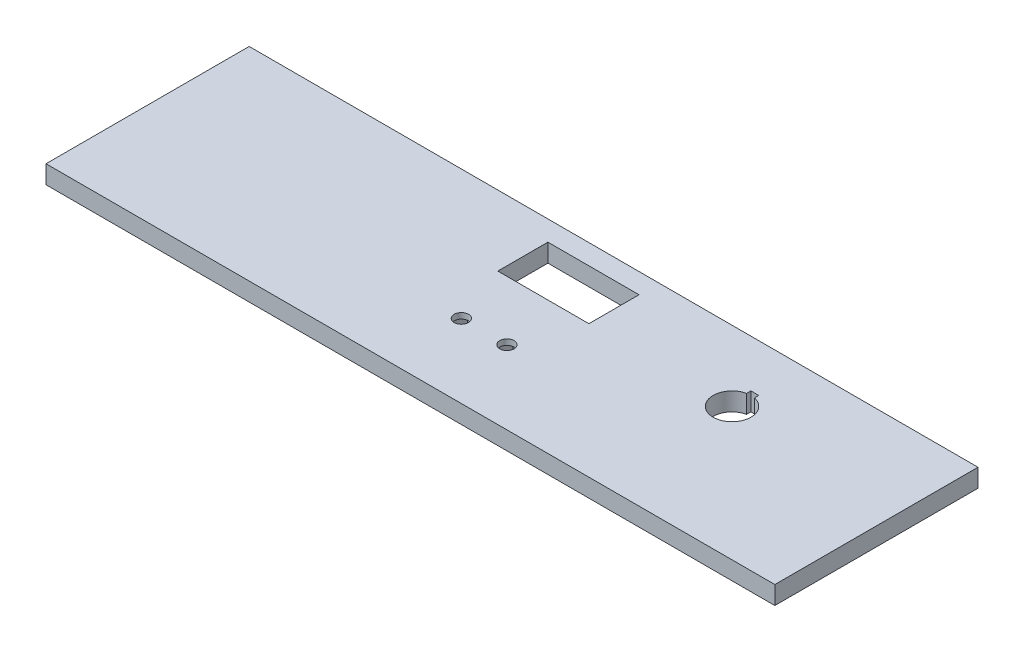
SolidWorks part; units mm, degrees
ref_plane "Front" through (0, 0, 0) normal (0, 0, 1) x (1, 0, 0)
ref_plane "Top" through (0, 0, 0) normal (0, 1, 0) x (1, 0, 0)
ref_plane "Right" through (0, 0, 0) normal (1, 0, 0) x (0, 0, -1)
sketch "Sketch2" plane through (0, 0, 0) normal (0, 1, 0) x (1, 0, 0)
  line L0 (51.5038, 15.0954) -> (51.5038, 13.8965)
  line L1 (-101.6, 28.321) -> (101.6, 28.321)
  line L2 (-101.6, 28.321) -> (-101.6, -28.321)
  line L3 (-101.6, -28.321) -> (101.6, -28.321)
  line L4 (101.6, 28.321) -> (101.6, -28.321)
  line L5 (-101.6, 28.321) -> (101.6, -28.321) construction
  line L6 (-101.6, -28.321) -> (101.6, 28.321) construction
  line L7 (51.5038, 15.0954) -> (53.7034, 15.0954)
  line L8 (52.6036, 8.742) -> (52.6036, 14.0125) construction
  line L9 (53.7034, 15.0954) -> (53.7034, 13.8965)
  line L10 (0, -55) -> (0, 55) construction
  line L11 (-12.7, 22.712) -> (12.7, 22.712)
  line L12 (-12.7, 22.712) -> (-12.7, 8.742)
  line L13 (-12.7, 8.742) -> (12.7, 8.742)
  line L14 (12.7, 22.712) -> (12.7, 8.742)
  line L15 (-12.7, 22.712) -> (12.7, 8.742) construction
  line L16 (-12.7, 8.742) -> (12.7, 22.712) construction
  circle A0 centre (52.6036, 8.742) radius 5.2705
  circle A1 centre (-6.35, -7.768) radius 2
  circle A2 centre (6.35, -7.768) radius 2
  point P0 (0, 0)
  point P13 (52.6036, 15.0954)
  point P14 (0, 15.727)
  point P25 (51.5038, 8.742)
  dimension "D1" = 10.541
  dimension "D8" = 4
  dimension "D2" = 1.1989
  dimension "D3" = 1.0998
  dimension "D4" = 25.4
  dimension "D5" = 13.97
  dimension "D6" = 203.2
  dimension "D7" = 56.642
  dimension "D9" = 16.51
  dimension "D10" = 6.35
extrude "Boss-Extrude1" add sketch "Sketch2" along normal blind 5.08 contours L4 L1 L2 L3 A0 L0 L7 L9 region at (-0.4276, 0, 0.5602)
sketch "Sketch4" plane through (0, 0, 0) normal (0, -1, 0) x (1, 0, 0)
  line L0 (0, -55) -> (0, 55) construction
  line L1 (-4.0117, 3.718) -> (-1.6735, 7.768)
  line L2 (-1.6735, 7.768) -> (-4.0117, 11.818)
  line L3 (-4.0117, 11.818) -> (-8.6883, 11.818)
  line L4 (101.6, -28.321) -> (101.6, 28.321)
  line L5 (101.6, 28.321) -> (-101.6, 28.321)
  line L6 (-101.6, 28.321) -> (-101.6, -28.321)
  line L7 (-101.6, -28.321) -> (101.6, -28.321)
  line L8 (101.6, -28.321) -> (101.6, 28.321)
  line L9 (101.6, 28.321) -> (-101.6, 28.321)
  line L10 (-101.6, 28.321) -> (-101.6, -28.321)
  line L11 (-101.6, -28.321) -> (101.6, -28.321)
  line L12 (-8.6883, 11.818) -> (-11.0265, 7.768)
  line L13 (-11.0265, 7.768) -> (-8.6883, 3.718)
  line L14 (-8.6883, 3.718) -> (-4.0117, 3.718)
  line L15 (4.0117, 3.718) -> (1.6735, 7.768)
  line L16 (8.6883, 3.718) -> (4.0117, 3.718)
  line L17 (11.0265, 7.768) -> (8.6883, 3.718)
  line L18 (8.6883, 11.818) -> (11.0265, 7.768)
  line L19 (4.0117, 11.818) -> (8.6883, 11.818)
  line L20 (1.6735, 7.768) -> (4.0117, 11.818)
  line L21 (101.6, 28.321) -> (101.6, -28.321)
  line L22 (-101.6, -28.321) -> (-101.6, 28.321)
  circle A0 centre (6.35, 7.768) radius 2 construction
  circle A1 centre (-6.35, 7.768) radius 2 construction
  circle A2 centre (6.35, 7.768) radius 2
  circle A3 centre (-6.35, 7.768) radius 2
  circle A4 centre (-6.35, 7.768) radius 4.05 construction
  dimension "D2" = 8.1
  dimension "D1" = 0
extrude "Cut-Extrude1" cut sketch "Sketch4" against normal blind 3.5 contours L2 L3 L12 L13 L14 L1 | L20 L19 L18 L17 L16 L15
sketch "Sketch5" plane through (0, 0, 28.321) normal (0, 0, 1) x (1, 0, 0)
  line L0 (0, -55) -> (0, 55) construction
  line L1 (-66.675, 5.08) -> (-60.325, 5.08)
  line L2 (-66.675, 5.08) -> (-66.675, -7.62)
  line L3 (-66.675, -7.62) -> (-60.325, -7.62)
  line L4 (-60.325, 5.08) -> (-60.325, -7.62)
  line L5 (66.675, -7.62) -> (60.325, -7.62)
  line L6 (60.325, 5.08) -> (60.325, -7.62)
  line L7 (66.675, 5.08) -> (60.325, 5.08)
  line L8 (-101.6, 0) -> (101.6, 0)
  line L9 (101.6, 0) -> (101.6, 5.08)
  line L10 (101.6, 5.08) -> (-101.6, 5.08)
  line L11 (-101.6, 5.08) -> (-101.6, 0)
  line L12 (-101.6, 0) -> (101.6, 0)
  line L13 (101.6, 0) -> (101.6, 5.08)
  line L14 (101.6, 5.08) -> (-101.6, 5.08)
  line L15 (-101.6, 5.08) -> (-101.6, 0)
  line L16 (66.675, 5.08) -> (66.675, -7.62)
  circle A0 centre (-63.5, -3.81) radius 1.5
  circle A1 centre (63.5, -3.81) radius 1.5
  point P18 (-63.5, -7.62)
  line M13 (-101.6, 0) -> (101.6, 0)
  line M15 (101.6, 5.08) -> (-101.6, 5.08)
  dimension "D4" = 3
  dimension "D2" = 6.35
  dimension "D3" = 12.7
  dimension "D5" = 3.81
  dimension "D6" = 63.5
  dimension "D1" = 0
extrude "Boss-Extrude2" add sketch "Sketch5" along normal blind 3.81 from surface contours L4 L2 L3 A0 M13 | L4 L2 M15 M13 | L16 L6 M15 M13 | L16 L6 L5 A1 M13 region at (-63.5, 2.54, 28.321) region at (-63.5, -0.0992, 28.321) region at (63.5, 2.54, 28.321) region at (63.5, -0.0992, 28.321) starting at face at (0, 2.54, -28.321)
